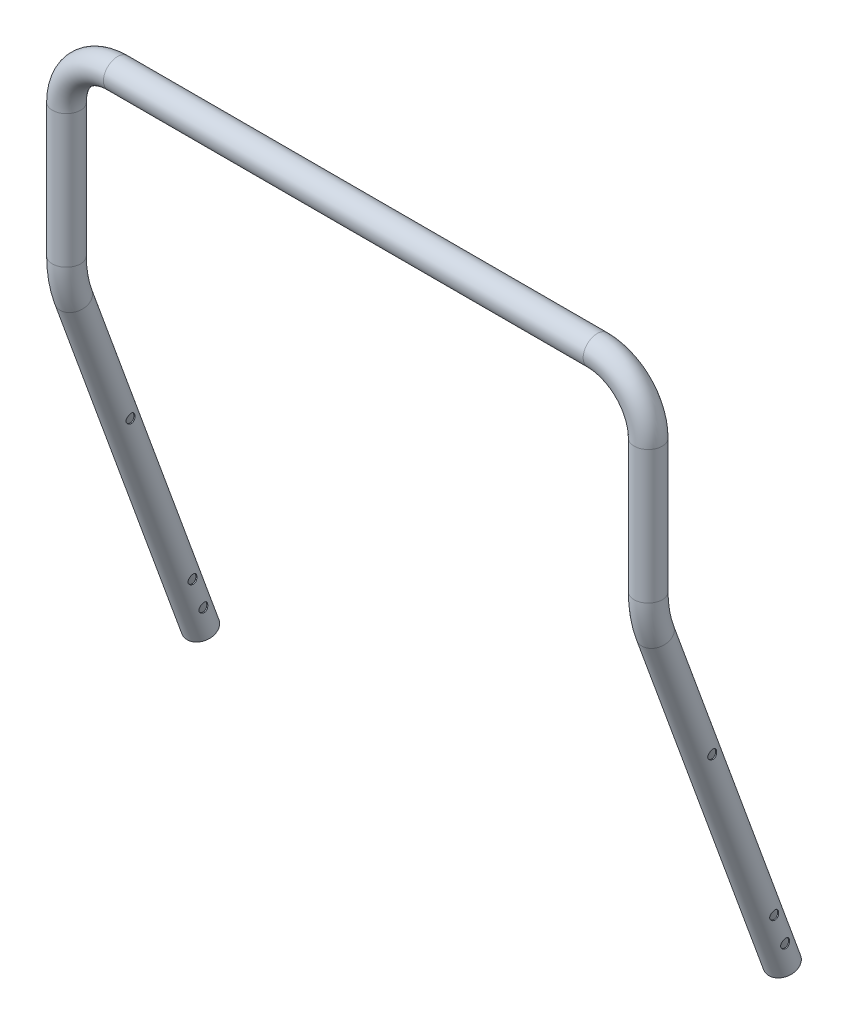
SolidWorks part; units mm, degrees
ref_plane "Front Plane" through (0, 0, 0) normal (0, 0, 1) x (1, 0, 0)
ref_plane "Top Plane" through (0, 0, 0) normal (0, 1, 0) x (1, 0, 0)
ref_plane "Right Plane" through (0, 0, 0) normal (1, 0, 0) x (0, 0, -1)
sketch "Sketch8" plane through (0, 0, 0) normal (0, 0, 1) x (1, 0, 0)
  line L0 (-188, 0) -> (188, 0)
  line L1 (-228, -40) -> (-228, -100)
  line L2 (228, -40) -> (228, -100)
  arc A0 (228, -40) -> (188, 0) centre (188, -40) ccw
  arc A1 (-188, 0) -> (-228, -40) centre (-188, -40) ccw
  point P4 (0, 0)
  point P9 (228, 0)
  point P12 (-228, 0)
  dimension "D2" = 40
  dimension "450" = 456
  dimension "D3" = 60
  dimension "D4" = 60
ref_plane "Plane3" through (228, -100, 0) normal (0, -1, 0) x (-1, 0, 0)
sketch "Sketch9" plane through (228, -100, 0) normal (0, -1, 0) x (-1, 0, 0)
  circle A0 centre (0, 0) radius 11
  circle A1 centre (0, 0) radius 10.2
  dimension "D1" = 0.8
ref_plane "Plane5" through (228, 0, 0) normal (1, 0, 0) x (0, 0, -1)
sketch "Sketch13" plane through (228, 0, 0) normal (1, 0, 0) x (0, 0, -1)
  line L0 (0, -100) -> (0, -144.2597)
  line L1 (-11, -100) -> (11, -100) construction
  line L2 (5.4277, -175.0415) -> (104.9678, -448.5257)
  arc A0 (5.4277, -175.0415) -> (0, -144.2597) centre (90, -144.2597) cw
  dimension "D1" = 90
  dimension "D2" = 160
sweep "Sweep2" add profiles "Sketch9" path "Sketch8"
sweep "Sweep3" add profiles "Sketch9<2>" path "Sketch13"
sketch "Sketch9<2>" plane through (228, -100, 0) normal (0, -1, 0) x (-1, 0, 0) same geometry as "Sketch9"
mirror "Mirror1" about plane through (0, 0, 0) normal (1, 0, 0) of "Sweep3"
sketch "Sketch14" plane through (228, 0, 0) normal (1, 0, 0) x (0, 0, -1)
  line L0 (104.9678, -448.5257) -> (5.4277, -175.0415) construction
  line L1 (94.6311, -452.2879) -> (115.3044, -444.7635) construction
  line L2 (15.7643, -171.2793) -> (-4.909, -178.8037) construction
  circle A0 centre (39.6596, -269.0931) radius 3.5
  circle A1 centre (88.2265, -402.5295) radius 3.5
  circle A3 centre (96.777, -426.0218) radius 3.5
  circle A4 centre (0, 0) radius 10.2 construction
  dimension "D1" = 142
  dimension "D2" = 25
  dimension "D3" = 272
extrude "Cut-Extrude1" cut sketch "Sketch14" against normal up to next and the other way up to next
mirror "Mirror2" about plane through (0, 0, 0) normal (1, 0, 0) of "Cut-Extrude1"
